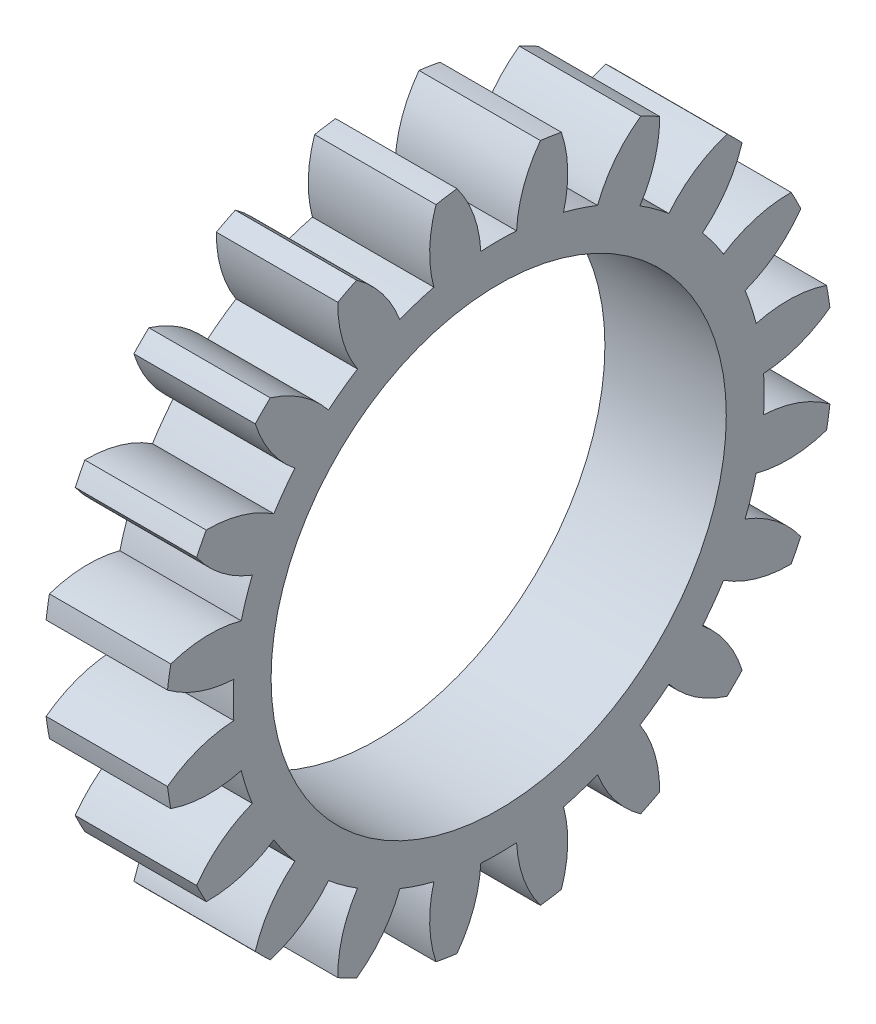
SolidWorks part; units mm, degrees
ref_plane "Plane1" through (0, 0, 0) normal (0, 0, 1) x (1, 0, 0)
ref_plane "Plane2" through (0, 0, 0) normal (0, 1, 0) x (1, 0, 0)
ref_plane "Plane3" through (0, 0, 0) normal (1, 0, 0) x (0, 0, -1)
other "Configuration Table"
sketch "HoldingSke" plane through (0, 0, 0) normal (0, 1, 0) x (1, 0, 0)
  line L0 (0, 0) -> (0.9397, -0.342)
  line L1 (-15, 0) -> (100, 0) construction
  line L2 (0, 0) -> (-2.1039, 2.3779)
  line L3 (0, 0) -> (-11.863, 4.5341)
  line L4 (0, 0) -> (8.1152, 2.9537)
  line L5 (0, 0) -> (-46.8476, -17.4728)
  line L6 (0, 0) -> (-3.3159, -2.2372)
  line L7 (-2.1039, 2.3779) -> (8.6586, 51.2059)
  line L8 (-76.2, 54.61) -> (-73.9, 54.61)
  line L9 (-67.7845, 28.3722) -> (-49.3413, 33.142)
  line L10 (-76.2, 71.12) -> (104.1128, 71.12)
  line L11 (0, 0) -> (-4, 0)
  line L12 (-76.2, 101.6) -> (-76.162, 101.6)
  line L13 (24.9733, 27.94) -> (52.9518, 28.4284)
  line L14 (24.9733, 27.94) -> (24.9743, 27.94)
  line L15 (24.9733, 27.94) -> (100.4006, 29.5858)
  line L16 (-63.627, -1) -> (-12.827, -1)
  circle A0 centre (0, 0) radius 7.5
  circle A1 centre (0, 0) radius 8.749
  circle A2 centre (0, 0) radius 37.5
  circle A3 centre (0, 0) radius 7.5
  dimension "Num_teeth" = 20
  dimension "Pitch_radius" = 180.3128
  dimension "Width" = 4
  dimension "Thickness" = 4
sketch "BasProSke" plane through (0, 0, 0) normal (0, 1, 0) x (1, 0, 0)
  line L0 (-10, 0) -> (60, 0) construction
  line L1 (0, 0) -> (0, 11)
  line L2 (0, 0) -> (4, 0)
  line L3 (4, 0) -> (4, 11)
  line L4 (4, 11) -> (0, 11)
  dimension "Thickness" = 4
  dimension "Diameter" = 22
revolve "Base-Revolve" add sketch "BasProSke" angle 360 about L0
sketch "TooCutSke" plane through (0, 0, 0) normal (1, 0, 0) x (0, 0, -1)
  line L1 (0, 0) -> (0, 107) construction
  line L2 (0, 0) -> (-0.8511, 9.9637) construction
  line L3 (0, 0) -> (-3.1206, 19.7028) construction
  line L4 (-0.8511, 9.9637) -> (-1.5603, 9.8514) construction
  arc A0 (0.5894, 8.7291) -> (-0.5894, 8.7291) centre (0, 0) ccw
  arc A1 (1.3917, 10.9372) -> (-1.3917, 10.9372) centre (0, 0) ccw
  circle A2 centre (0, 0) radius 10 construction
  circle A3 centre (0, 0) radius 9.6815 construction
  arc A4 (-0.5894, 8.7291) -> (-1.3917, 10.9372) centre (-4.5843, 8.5273) ccw
  arc A5 (1.3917, 10.9372) -> (0.5894, 8.7291) centre (4.5843, 8.5273) ccw
extrude "ToothCut" cut sketch "TooCutSke" along normal through all
fillet "Breaks" [suppressed] radius 0.02 tangent propagation no
fillet "RootFillets" [suppressed] radius 0.251
pattern_circular "TeethCuts" count 20 every 18 about axis through (-10, 0, 0) along (1, 0, 0) of "ToothCut", "RootFillets", "Breaks"
sketch "HubNeaOneSke" plane through (0, 0, 0) normal (-1, 0, 0) x (0, 0, 1)
  circle A0 centre (0, 0) radius 8.749
  dimension "Diameter" = 17.498
extrude "HubNearOne" [suppressed] add sketch "HubNeaOneSke" along normal blind 46.0001
sketch "HubNeaBotSke" plane through (0, 0, 0) normal (-1, 0, 0) x (0, 0, 1)
  circle A0 centre (0, 0) radius 8.749
  dimension "Diameter" = 17.498
extrude "HubNearBoth" [suppressed] add sketch "HubNeaBotSke" along normal blind 23
ref_plane "FarPln" through (4, 0, 0) normal (1, 0, 0) x (0, 0, -1)
sketch "HubFarSke" plane through (4, 0, 0) normal (1, 0, 0) x (0, 0, -1)
  circle A0 centre (0, 0) radius 8.749
  dimension "Diameter" = 17.498
extrude "HubFar" [suppressed] add sketch "HubFarSke" along normal blind 23
sketch "BorSke" plane through (0, 0, 0) normal (1, 0, 0) x (0, 0, -1)
  circle A0 centre (0, 0) radius 7.5
  dimension "Diameter" = 15
extrude "Bore" cut sketch "BorSke" along normal mid plane 100.0001
sketch "KeySke" plane through (0, 0, 0) normal (1, 0, 0) x (0, 0, -1)
  line L0 (-2.5, 0) -> (-2.5, 9.8)
  line L1 (-2.5, 9.8) -> (2.5, 9.8)
  line L2 (2.5, 9.8) -> (2.5, 0)
  line L3 (0, 0) -> (0, 34) construction
  line L4 (-2.5, 0) -> (2.5, 0)
  dimension "Width" = 5
extrude "Keyway" [suppressed] cut sketch "KeySke" along normal mid plane 100.0001
pattern_circular "Keyway2" [suppressed] count 2 every 90 about axis through (-10, 0, 0) along (1, 0, 0) reverse direction yes
equation "' \"Module@HoldingSke\" = 6.35"
equation "' \"Num_teeth@HoldingSke\" = 12"
equation "' \"Ap@HoldingSke\" =  20"
equation "' \"Ap@HoldingSke\" = 20"
equation "' \"Width@HoldingSke\" = 0.5 * 25.4"
equation "' \"Hub_dia@HoldingSke\"= 1 * 25.4"
equation "' \"Hub_dia@HoldingSke\" = 1 * 25.4"
equation "' \"Overall_len@HoldingSke\" = 1.0 * 25.4"
equation "' \"Bore@HoldingSke\" = 0.75 * 25.4"
equation "' \"T_dim@HoldingSke\" = 0.1 * 25.4"
equation "' \"Width@KeySke\" = 0.25 * 25.4"
equation "' \"Show_teeth@HoldingSke\" = 13"
equation "' \"Backlash@HoldingSke\" = 0.009 * 25.4"
equation "' \"Addendum_fac@HoldingSke\" = 1.0"
equation "' \"Dedendum_fac@HoldingSke\" = 1.25"
equation "' \"Dedendum_add@HoldingSke\" = 0.00005 * 25.4"
equation "' \"Clearance_fac@HoldingSke\" = 0.25"
equation "\"Pitch@HoldingSke\" = 1 / \"Module@HoldingSke\""
equation "\"Overcut_dia@TooCutSke\" = (\"Num_teeth@HoldingSke\" + 2 * \"Addendum_fac@HoldingSke\") / \"Pitch@HoldingSke\" + 0.002 * 25.4"
equation "\"Pitch_dia@TooCutSke\" = \"Num_teeth@HoldingSke\" / \"Pitch@HoldingSke\""
equation "\"Base_dia@TooCutSke\" = \"Num_teeth@HoldingSke\" / \"Pitch@HoldingSke\" * cos((\"Ap@HoldingSke\"  * 3.14159265 / 180))"
equation "\"Root_dia@TooCutSke\" = (\"Num_teeth@HoldingSke\" + 2) / \"Pitch@HoldingSke\" - 2 * (\"Addendum_fac@HoldingSke\" + \"Dedendum_fac@HoldingSke\") / \"Pitch@HoldingSke\" - \"Dedendum_add@HoldingSke\" * 2"
equation "\"Half_ang@TooCutSke\" = 180 / \"Num_teeth@HoldingSke\""
equation "\"Half_CT@TooCutSke\" = \"Num_teeth@HoldingSke\" / \"Pitch@HoldingSke\" * sin((3.14159265 / 2 / \"Num_teeth@HoldingSke\")) / 2 - 7 * \"Backlash@HoldingSke\" / 4"
equation "\"Flank_rad@TooCutSke\" = \"Num_teeth@HoldingSke\" / \"Pitch@HoldingSke\" / 5"
equation "\"Radius@RootFillets\" = \"Clearance_fac@HoldingSke\" / \"Pitch@HoldingSke\" + \"Dedendum_add@HoldingSke\""
equation "\"Break_rad@Breaks\" = 0.02 / \"Pitch@HoldingSke\""
equation "\"Thickness@HoldingSke\" = \"Width@HoldingSke\""
equation "\"OAL@HoldingSke\" = \"Thickness@HoldingSke\""
equation "\"MHD@HoldingSke\" = (\"Num_teeth@HoldingSke\" + 2) / \"Pitch@HoldingSke\" - 2 * (\"Addendum_fac@HoldingSke\" + \"Dedendum_fac@HoldingSke\")  / \"Pitch@HoldingSke\" - \"Dedendum_add@HoldingSke\" * 2"
equation "\"MBD@HoldingSke\" = (\"Num_teeth@HoldingSke\" + 2) / \"Pitch@HoldingSke\" - 2 * (\"Addendum_fac@HoldingSke\" + \"Dedendum_fac@HoldingSke\")  / \"Pitch@HoldingSke\" - \"Dedendum_add@HoldingSke\" * 2 - 0.002 * 25.4"
equation "\"MHD@HoldingSke\" = ((sgn( \"MHD@HoldingSke\" - \"Hub_dia@HoldingSke\" )-1)*( \"MHD@HoldingSke\" - \"Hub_dia@HoldingSke\" ))/-2+ \"Hub_dia@HoldingSke\""
equation "\"MBD@HoldingSke\" = ((sgn( \"MBD@HoldingSke\" - \"Bore@HoldingSke\" )-1)*( \"MBD@HoldingSke\" - \"Bore@HoldingSke\" ))/-2+ \"Bore@HoldingSke\""
equation "\"OAL@HoldingSke\" = ((sgn( \"OAL@HoldingSke\" - \"Overall_len@HoldingSke\" )+1)*( \"OAL@HoldingSke\" - \"Overall_len@HoldingSke\" ))/2 + \"Overall_len@HoldingSke\" + 0.000002 * 25.4"
equation "\"Num_teeth@TeethCuts\" = int( \"Show_teeth@HoldingSke\" ) + 1"
equation "\"Num_teeth@TeethCuts\" = ((sgn( \"Num_teeth@TeethCuts\" - \"Num_teeth@HoldingSke\" )-1)*( \"Num_teeth@TeethCuts\" - \"Num_teeth@HoldingSke\" ))/-2+ \"Num_teeth@HoldingSke\""
equation "\"Num_teeth@TeethCuts\" = ((sgn( \"Num_teeth@TeethCuts\" - 2.0)+1)*( \"Num_teeth@TeethCuts\" - 2.0))/2 +2.0"
equation "\"Angle@TeethCuts\" = 360.0 / \"Num_teeth@HoldingSke\""
equation "\"Diameter@BasProSke\" = (\"Num_teeth@HoldingSke\" + 2 * \"Addendum_fac@HoldingSke\") / \"Pitch@HoldingSke\""
equation "\"Thickness@BasProSke\"  = \"Thickness@HoldingSke\""
equation "' \"Fillet_rad@BasProSke\" =  \"Thickness@HoldingSke\" * 0.05"
equation "' \"Fillet_rad@BasProSke\" = \"Thickness@HoldingSke\" * 0.05"
equation "\"MHD@HoldingSke\" = ((sgn( \"MHD@HoldingSke\" - \"Root_dia@TooCutSke\" )-1)*( \"MHD@HoldingSke\" - \"Root_dia@TooCutSke\" ))/-2+ \"Root_dia@TooCutSke\""
equation "\"Diameter@HubNeaOneSke\" = \"MHD@HoldingSke\""
equation "\"Length@HubNearOne\" = \"OAL@HoldingSke\" - \"Thickness@BasProSke\""
equation "\"Diameter@HubNeaBotSke\" = \"MHD@HoldingSke\""
equation "\"Length@HubNearBoth\" = ( \"OAL@HoldingSke\" - \"Thickness@BasProSke\" ) / 2.0"
equation "\"Thickness@FarPln\" = \"Thickness@BasProSke\""
equation "\"Diameter@HubFarSke\" = \"MHD@HoldingSke\""
equation "\"Length@HubFar\" = ( \"OAL@HoldingSke\" - \"Thickness@BasProSke\" ) / 2.0"
equation "\"Diameter@BorSke\" = \"MBD@HoldingSke\""
equation "\"D1@Bore\" = \"OAL@HoldingSke\" * 2.0"
equation "\"D1@Keyway\" = \"OAL@HoldingSke\" * 2.0"
equation "\"Offset@KeySke\" = \"T_dim@HoldingSke\" + \"MBD@HoldingSke\" / 2.0"
